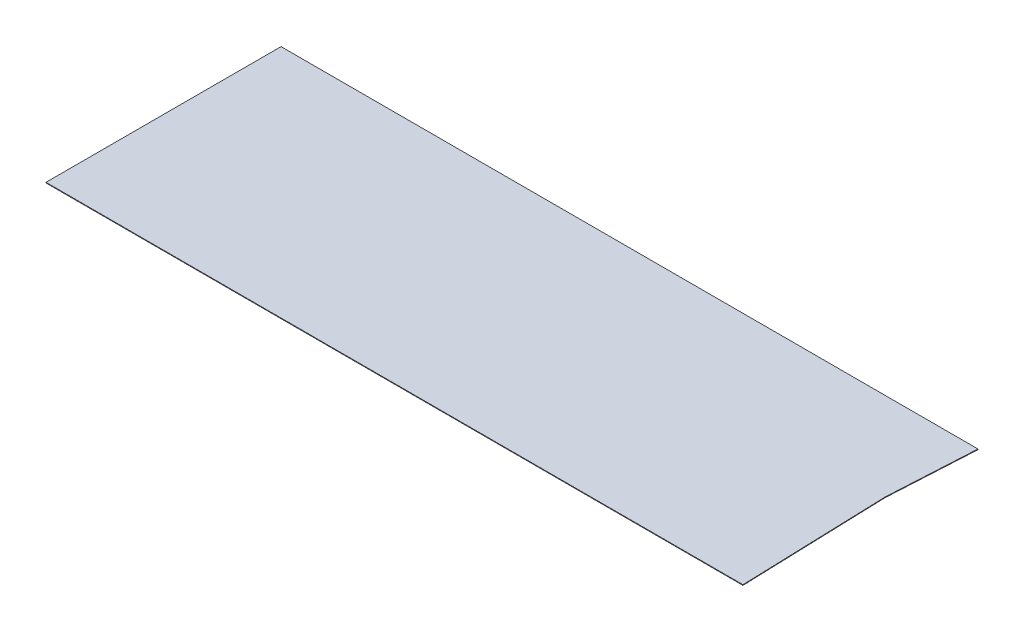
SolidWorks part; units mm, degrees
material "solkoted PC"
ref_plane "Front Plane" through (0, 0, 0) normal (0, 0, 1) x (1, 0, 0)
ref_plane "Top Plane" through (0, 0, 0) normal (0, 1, 0) x (1, 0, 0)
ref_plane "Right Plane" through (0, 0, 0) normal (1, 0, 0) x (0, 0, -1)
ref_axis "Axis1" through (0, -55, 0) along (0, 1, 0)
sketch "Sketch1" plane through (0, 0, 0) normal (0, 1, 0) x (1, 0, 0)
  line L0 (909.7666, -304.8) -> (897.0666, 76.2)
  line L1 (-897.89, 304.8) -> (909.7666, 304.8)
  line L2 (-897.89, 304.8) -> (-897.89, -304.8)
  line L3 (-897.89, -304.8) -> (909.7666, -304.8)
  line L5 (-897.89, 304.8) -> (909.7666, -304.8) construction
  line L6 (-897.89, -304.8) -> (909.7666, 304.8) construction
  line L7 (897.0666, 76.2) -> (909.7666, 304.8)
  line L8 (909.7666, -304.8) -> (909.7666, 304.8) construction
  line L9 (916.1166, 285.75) -> (916.1166, -285.75)
  line L10 (916.1166, 285.75) -> (916.1166, -285.75) construction
  point P0 (3.81, 0)
  dimension "D1" = 6.35
  dimension "D2" = 609.6
  dimension "D3" = 25.4
  dimension "D4" = 228.6
  dimension "D5" = 897.89
  dimension "D6" = 304.8
extrude "Boss-Extrude1" add sketch "Sketch1" along normal blind 1.5875
